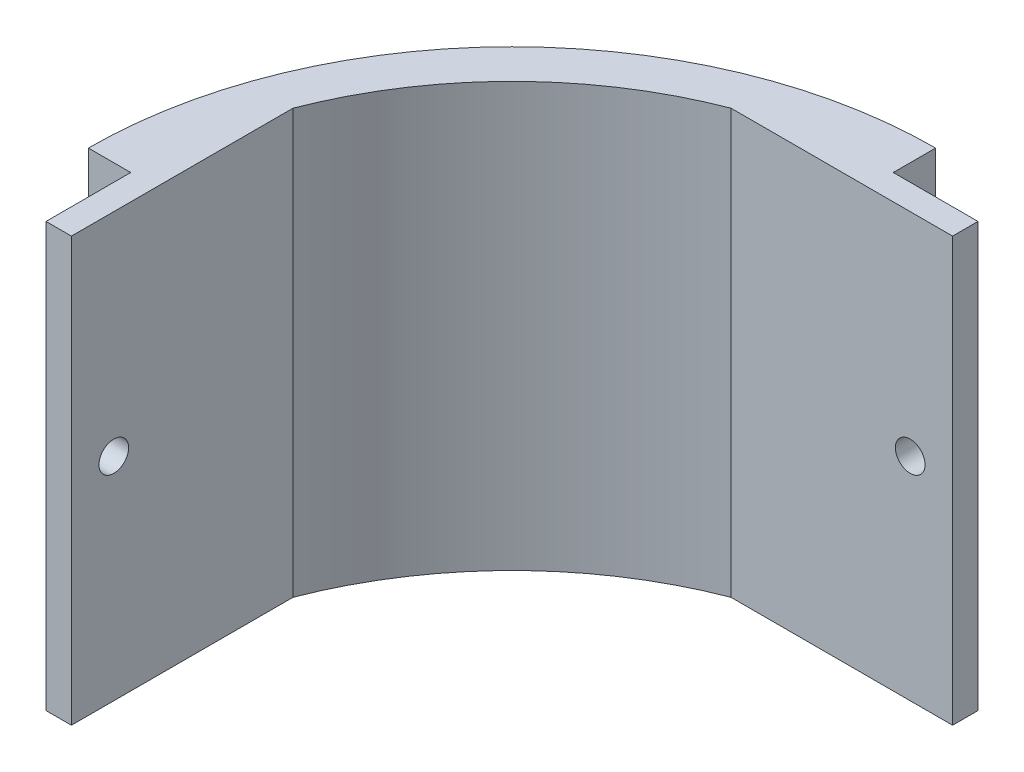
SolidWorks part; units mm, degrees
ref_plane "Front Plane" through (0, 0, 0) normal (0, 0, 1) x (1, 0, 0)
ref_plane "Top Plane" through (0, 0, 0) normal (0, 1, 0) x (1, 0, 0)
ref_plane "Right Plane" through (0, 0, 0) normal (1, 0, 0) x (0, 0, -1)
sketch "Sketch1" plane through (0, 0, 0) normal (0, 1, 0) x (1, 0, 0)
  line L0 (0, 0) -> (0, 50) construction
  line L1 (0, 0) -> (-50, 0) construction
  line L2 (-50, 0) -> (-45, 0)
  line L3 (0, 50) -> (0, 45)
  arc A0 (0, 50) -> (-50, 0) centre (0, 0) ccw
  arc A1 (0, 45) -> (-45, 0) centre (0, 0) ccw
  point P4 (-45, 0)
  point P5 (-50, 0)
  dimension "D1" = 100
  dimension "D2" = 5
extrude "Boss-Extrude1" add sketch "Sketch1" along normal blind 50
sketch "Sketch2" plane through (0, 0, 0) normal (0, 0, 1) x (1, 0, 0)
  line L0 (-50, 50) -> (-45, 50) construction
  line L1 (-45, 0) -> (-42, 0)
  line L2 (-45, 0) -> (-45, 50)
  line L3 (-45, 50) -> (-42, 50)
  line L4 (-42, 0) -> (-42, 50)
  dimension "D1" = 3
extrude "Boss-Extrude2" add sketch "Sketch2" along normal blind 10 and the other way up to next
sketch "Sketch4" plane through (0, 0, 0) normal (1, 0, 0) x (0, 0, -1)
  line L0 (16.1555, 0) -> (45, 0) construction
  line L1 (45, 50) -> (42, 50)
  line L2 (45, 50) -> (45, 0)
  line L3 (45, 0) -> (42, 0)
  line L4 (42, 50) -> (42, 0)
  dimension "D1" = 3
extrude "Boss-Extrude3" add sketch "Sketch4" along normal blind 10 and the other way up to next
sketch "Sketch5" plane through (0, 0, -45) normal (0, 0, -1) x (-1, 0, 0)
  line L1 (-10, 0) -> (-10, 50) construction
  circle A0 centre (-5, 25) radius 1.75
  point P8 (-10, 25)
  dimension "D1" = 3.5
  dimension "D2" = 5
extrude "Cut-Extrude1" cut sketch "Sketch5" against normal blind 10
sketch "Sketch6" plane through (-45, 0, 0) normal (-1, 0, 0) x (0, 0, 1)
  line L0 (10, 50) -> (10, 0) construction
  circle A0 centre (5, 25) radius 1.75
  point P6 (10, 25)
  dimension "D1" = 3.5
  dimension "D2" = 5
extrude "Cut-Extrude2" cut sketch "Sketch6" against normal blind 10
